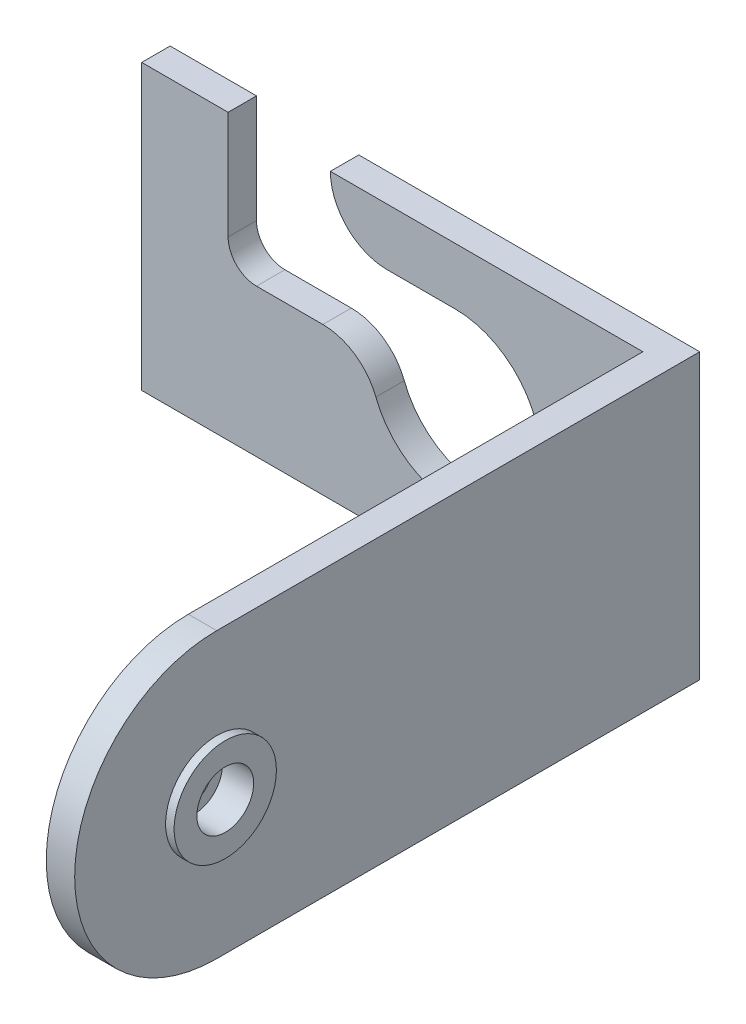
SolidWorks part; units mm, degrees
ref_plane "Front Plane" through (0, 0, 0) normal (0, 0, 1) x (1, 0, 0)
ref_plane "Top Plane" through (0, 0, 0) normal (0, 1, 0) x (1, 0, 0)
ref_plane "Right Plane" through (0, 0, 0) normal (1, 0, 0) x (0, 0, -1)
sketch "Sketch1" plane through (0, 0, 0) normal (1, 0, 0) x (0, 0, -1)
  line L1 (0, 12.5) -> (42.5, 12.5)
  line L2 (0, 1.5) -> (0, -12.5)
  line L3 (0, -12.5) -> (42.5, -12.5)
  line L4 (42.5, 12.5) -> (42.5, -12.5)
  circle A0 centre (0, 0) radius 1.5
  circle A1 centre (0, 0) radius 12.5 construction
  arc A2 (0, 12.5) -> (0, -12.5) centre (0, 0) ccw
  dimension "D1" = 3
  dimension "D2" = 25
  dimension "D3" = 42.5
extrude "Boss-Extrude1" add sketch "Sketch1" along normal blind 2.5 contours L1 A2 A0 L3 L4 region at (0, 0, -16.3553)
sketch "Sketch2" plane through (0, 0, 0) normal (-1, 0, 0) x (0, 0, 1)
  circle A0 centre (0, 0) radius 1.5
  circle A1 centre (0, 0) radius 4.5
  dimension "D1" = 9
  dimension "D2" = 3
extrude "Boss-Extrude2" add sketch "Sketch2" along normal blind 1.8 and the other way offset from surface 0.75 other way up to face at (2.5, 0, -18.125)
sketch "Sketch4" plane through (2.5, 0, 0) normal (1, 0, 0) x (0, 0, -1)
  circle A0 centre (0, 0) radius 2.5
extrude "Cut-Extrude1" cut sketch "Sketch4" against normal blind 2
sketch "Sketch5" plane through (2.5, 0, 0) normal (1, 0, 0) x (0, 0, -1)
  circle A0 centre (0, 0) radius 4.5
  circle A1 centre (0, 0) radius 2.5
  dimension "D1" = 9
  dimension "D2" = 5
extrude "Boss-Extrude3" add sketch "Sketch5" along normal blind 0.75
sketch "Sketch6" plane through (0, 0, -42.5) normal (0, 0, -1) x (-1, 0, 0)
  line L0 (-2.5, 12.5) -> (0, 12.5) construction
  line L1 (-2.5, 12.5) -> (44.1, 12.5)
  line L2 (-2.5, 12.5) -> (-2.5, -12.5)
  line L3 (-2.5, -12.5) -> (44.1, -12.5)
  line L4 (44.1, 12.5) -> (44.1, -12.5)
  dimension "D1" = 46.6
extrude "Boss-Extrude4" add sketch "Sketch6" against normal blind 2.5
ref_plane "Plane1" through (-16.5, 0, 0) normal (1, 0, 0) x (0, 0, -1)
ref_plane "Plane2" through (10.05, 0, 0) normal (1, 0, 0) x (0, 0, -1)
sketch "Sketch7" plane through (0, 0, -40) normal (0, 0, 1) x (1, 0, 0)
  line L4 (-27.5, 12.5) -> (-36.5, 12.5)
  line L13 (-22.5, 7.5) -> (-16.5, 7.5)
  line L14 (-28.1619, 0.5) -> (-34, 0.5)
  line L17 (-36.5, 3) -> (-36.5, 12.5)
  arc A6 (-23.4971, -2.7) -> (-28.1619, 0.5) centre (-28.1619, -4.5) ccw
  arc A7 (-23.4971, -2.7) -> (-16.5, 7.5) centre (-16.5, 0) ccw
  arc A8 (-27.5, 12.5) -> (-22.5, 7.5) centre (-22.5, 12.5) ccw
  arc A11 (-36.5, 3) -> (-34, 0.5) centre (-34, 3) ccw
extrude "Cut-Extrude2" cut sketch "Sketch7" against normal up to next
